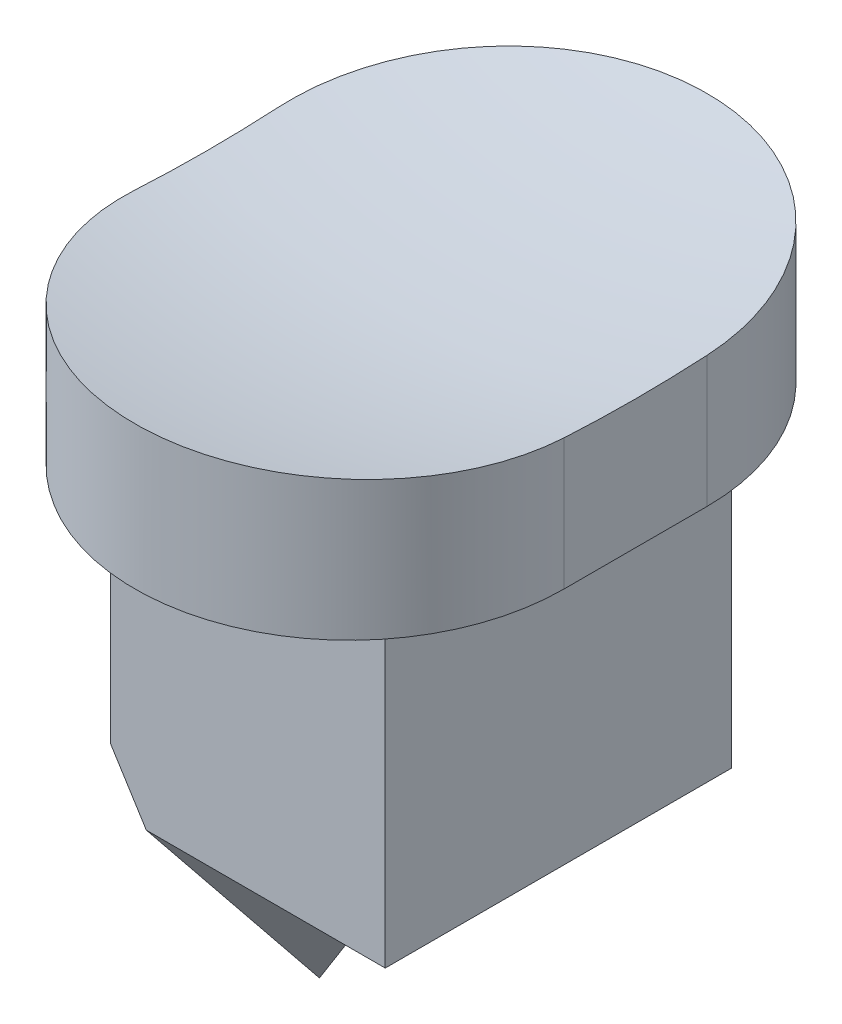
SolidWorks part; units mm, degrees
ref_plane "Front Plane" through (0, 0, 0) normal (0, 0, 1) x (1, 0, 0)
ref_plane "Top Plane" through (0, 0, 0) normal (0, 1, 0) x (1, 0, 0)
ref_plane "Right Plane" through (0, 0, 0) normal (1, 0, 0) x (0, 0, -1)
sketch "Sketch1" plane through (0, 0, 0) normal (0, 1, 0) x (1, 0, 0)
  line L1 (-9.6, 12.1) -> (9.6, 12.1)
  line L2 (-9.6, 12.1) -> (-9.6, -12.1)
  line L3 (-9.6, -12.1) -> (9.6, -12.1)
  line L4 (9.6, 12.1) -> (9.6, -12.1)
  line L5 (-9.6, 12.1) -> (9.6, -12.1) construction
  line L6 (-9.6, -12.1) -> (9.6, 12.1) construction
  point P0 (0, 0)
  dimension "D1" = 19.2
  dimension "D2" = 24.2
extrude "Boss-Extrude1" add sketch "Sketch1" along normal blind 22.1
sketch "Sketch2" plane through (0, 22.1, 0) normal (0, 1, 0) x (1, 0, 0)
  line L0 (0, 5) -> (0, -5) construction
  line L1 (15, 5) -> (15, -5)
  line L2 (-15, 5) -> (-15, -5)
  line L3 (0, 20) -> (0, -20) construction
  line L4 (-9.6, 0) -> (9.6, 0) construction
  line L5 (-9.6, 12.1) -> (-9.6, -12.1) construction
  line L6 (9.6, -12.1) -> (9.6, 12.1) construction
  arc A0 (15, 5) -> (-15, 5) centre (0, 5) ccw
  arc A1 (-15, -5) -> (15, -5) centre (0, -5) ccw
  point P3 (0, 0)
  dimension "D1" = 30
  dimension "D2" = 40
extrude "Boss-Extrude2" add sketch "Sketch2" along normal blind 10
sketch "Sketch4" plane through (-9.6, 0, 0) normal (-1, 0, 0) x (0, 0, 1)
  line L0 (0, 0) -> (0, -15) construction
  line L1 (-12.1, 0) -> (0, -15)
  line L2 (0, -15) -> (12.1, 0)
  line L3 (12.1, 0) -> (-12.1, 0)
  dimension "D1" = 15
extrude "Boss-Extrude3" add sketch "Sketch4" against normal blind 5
sketch "Sketch6" plane through (0, 0, 0) normal (0, 0, 1) x (1, 0, 0)
  line L0 (-4.6, -5) -> (9.6, 0)
  line L1 (-4.6, -15) -> (-4.6, 0) construction
  line L3 (-4.6, -5) -> (-4.6, 0)
  line L4 (-4.6, 0) -> (9.6, 0)
  dimension "D1" = 10
extrude "Boss-Extrude4" add sketch "Sketch6" along normal mid plane 3
chamfer "Chamfer1" distance 2.5 angle 45 4 edges at (-9.6, -7.5, -6.05) (-9.6, -7.5, 6.05) (-4.6, -7.5, -6.05) (-4.6, -7.5, 6.05)
fillet "Fillet1" radius 3 2 edges at (-4.6, 0, -5.194) (-4.6, 0, 5.194)
sketch "Sketch8" plane through (0, 0, 0) normal (1, 0, 0) x (0, 0, -1)
  line L0 (-90.1466, 120) -> (90.1466, 120) construction
  line L1 (-90.1466, 120) -> (90.1466, 120)
  line L2 (0, 120) -> (0, 29.8534) construction
  arc A0 (-90.1466, 120) -> (90.1466, 120) centre (0, 120) ccw
  dimension "D1" = 120
revolve "Cut-Revolve3" cut sketch "Sketch8" angle 360 about L1
equation "\"Hole Length\"= 25"
equation "\"Hole Height\"= 20"
equation "\"Shell Thickness\"= 5"
equation "\"Can Diameter\"= 66.3"
equation "\"Hole Tolerance\" = 0.8"
equation "\"D1@Sketch1\"=\"Hole Height\"-\"Hole Tolerance\""
equation "\"D2@Sketch1\"=\"Hole Length\"-\"Hole Tolerance\""
equation "\"D1@Sketch2\"=\"Hole Height\"+10"
equation "\"D2@Sketch2\"=\"Hole Length\"+15"
equation "\"D1@Boss-Extrude1\"=\"Shell Thickness\"+17.1"
equation "\"Blade thickness\"= 5"
equation "\"D1@Boss-Extrude3\"=\"Blade thickness\""
